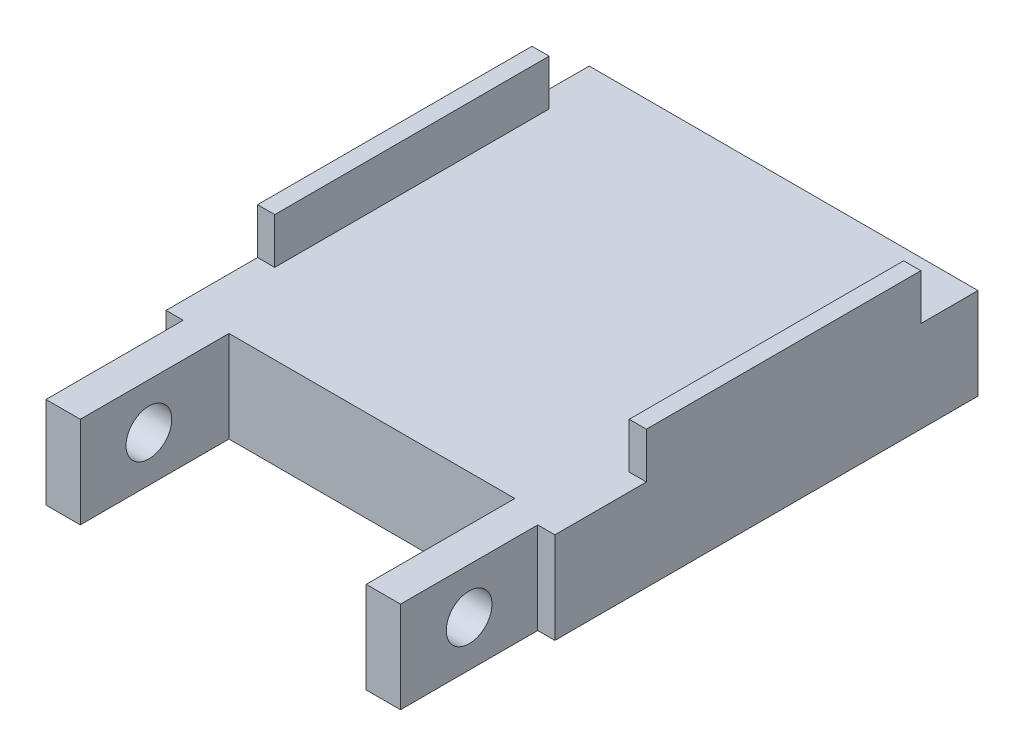
SolidWorks part; units mm, degrees
ref_plane "前视基准面" through (0, 0, 0) normal (0, 0, 1) x (1, 0, 0)
ref_plane "上视基准面" through (0, 0, 0) normal (0, 1, 0) x (1, 0, 0)
ref_plane "右视基准面" through (0, 0, 0) normal (1, 0, 0) x (0, 0, -1)
sketch "草图1" plane through (0, 0, 0) normal (0, 1, 0) x (1, 0, 0)
  line L1 (17, -24.5) -> (-17, -24.5)
  line L2 (17, -24.5) -> (17, 24.5)
  line L3 (17, 24.5) -> (-17, 24.5)
  line L4 (-17, -24.5) -> (-17, 24.5)
  line L5 (0, 24.5) -> (0, -24.5) construction
  line L6 (17, 0) -> (-17, 0) construction
  point P0 (0, 0)
  dimension "D1" = 49
  dimension "D2" = 34
extrude "凸台-拉伸1" add sketch "草图1" along normal blind 8
sketch "草图2" plane through (0, 8, 0) normal (0, 1, 0) x (1, 0, 0)
  line L0 (-17, 24.5) -> (-17, -24.5) construction
  line L1 (-17, 19.5) -> (-15.5, 19.5)
  line L2 (-17, 19.5) -> (-17, -4.5)
  line L3 (-17, -4.5) -> (-15.5, -4.5)
  line L4 (-15.5, 19.5) -> (-15.5, -4.5)
  line L5 (17, 24.5) -> (-17, 24.5) construction
  line L6 (0, -55) -> (0, 55) construction
  line L7 (17, -4.5) -> (15.5, -4.5)
  line L8 (15.5, 19.5) -> (15.5, -4.5)
  line L9 (17, 19.5) -> (17, -4.5)
  line L10 (17, 19.5) -> (15.5, 19.5)
  dimension "D1" = 1.5
  dimension "D2" = 24
  dimension "D3" = 5
extrude "凸台-拉伸2" add sketch "草图2" along normal blind 4
sketch "草图3" plane through (0, 8, 0) normal (0, 1, 0) x (1, 0, 0)
  line L0 (-17, -24.5) -> (17, -24.5) construction
  line L1 (-17, -24.5) -> (-15.5, -24.5)
  line L2 (-17, -24.5) -> (-17, -12.5)
  line L3 (-17, -12.5) -> (-15.5, -12.5)
  line L4 (-15.5, -24.5) -> (-15.5, -12.5)
  line L5 (17, -24.5) -> (15.5, -24.5)
  line L6 (17, -24.5) -> (17, -12.5)
  line L7 (17, -12.5) -> (15.5, -12.5)
  line L8 (15.5, -24.5) -> (15.5, -12.5)
  line L10 (-12.5, -24.5) -> (12.5, -24.5)
  line L11 (-12.5, -24.5) -> (-12.5, -11.5)
  line L12 (-12.5, -11.5) -> (12.5, -11.5)
  line L13 (12.5, -24.5) -> (12.5, -11.5)
  dimension "D1" = 1.5
  dimension "D2" = 1.5
  dimension "D3" = 12
  dimension "D4" = 12
  dimension "D5" = 13
  dimension "D6" = 3
  dimension "D7" = 3
extrude "切除-拉伸1" cut sketch "草图3" against normal up to surface (8 mm away) up to face at (0, 0, 0)
sketch "草图4" plane through (-15.5, 0, 0) normal (-1, 0, 0) x (0, 0, 1)
  line L0 (24.5, 0) -> (24.5, 8) construction
  line L1 (24.5, 8) -> (12.5, 8) construction
  circle A0 centre (18.5, 4) radius 2
  dimension "D1" = 6
  dimension "D2" = 4
  dimension "D3" = 4
extrude "切除-拉伸2" cut sketch "草图4" against normal up to surface (31 mm away) up to face at (15.5, 4, 18.5)
sketch "草图5" plane through (0, 0, 0) normal (0, -1, 0) x (1, 0, 0)
  line L0 (-12.5, 11.5) -> (12.5, 11.5) construction
  line L1 (4, 11.5) -> (-4, 11.5)
  line L2 (4, 11.5) -> (4, 41.5)
  line L4 (-4, 11.5) -> (-4, 41.5)
  line L5 (13, 41.5) -> (4, 41.5)
  line L7 (13, 41.5) -> (13, 56.5)
  line L8 (13, 56.5) -> (-13, 56.5)
  line L9 (-13, 41.5) -> (-13, 56.5)
  line L10 (-4, 41.5) -> (-13, 41.5)
  point P6 (0, 11.5)
  dimension "D1" = 8
  dimension "D2" = 30
  dimension "D3" = 26
  dimension "D4" = 15
  dimension "D5" = 9
extrude "凸台-拉伸3" add sketch "草图5" against normal blind 8
sketch "草图6" plane through (0, 0, 0) normal (0, -1, 0) x (1, 0, 0)
  line L0 (4, 11.5) -> (4, 41.5) construction
  line L1 (17, -24.5) -> (-17, -24.5) construction
  circle A0 centre (0, -9.5) radius 1.5
  circle A1 centre (5, -9.5) radius 0.5
  circle A2 centre (11, -9.5) radius 0.5
  circle A3 centre (-4.5, -9.5) radius 0.5
  circle A4 centre (-10.5, -9.5) radius 0.5
  circle A5 centre (0, -14) radius 0.5
  circle A6 centre (0, -5) radius 0.5
  dimension "D1" = 4
  dimension "D2" = 4.5
  dimension "D3" = 10.5
  dimension "D4" = 5
  dimension "D5" = 11
  dimension "D6" = 1
  dimension "D7" = 1
  dimension "D8" = 1
  dimension "D9" = 1
  dimension "D10" = 3
  dimension "D11" = 1
  dimension "D12" = 1
  dimension "D13" = 4.5
  dimension "D14" = 4.5
  dimension "D15" = 15
extrude "切除-拉伸3" cut sketch "草图6" against normal blind 5
extrude "切除-拉伸4" cut sketch "草图5<2>" against normal up to surface (8 mm away) up to face at (0, 8, 13)
sketch "草图5<2>" plane through (0, 0, 0) normal (0, -1, 0) x (1, 0, 0) same geometry as "草图5"
